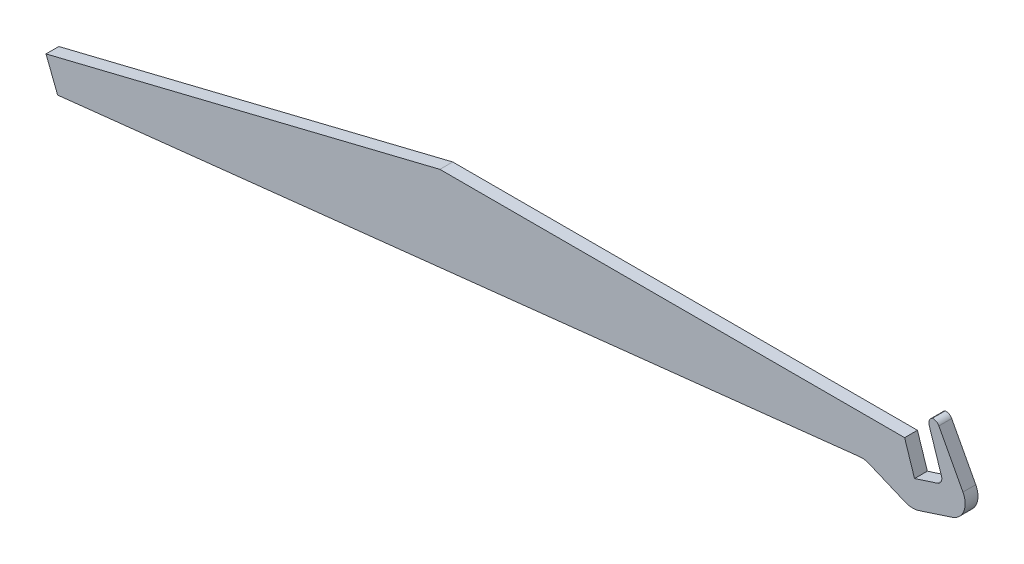
SolidWorks part; units mm, degrees
ref_plane "Front Plane" through (0, 0, 0) normal (0, 0, 1) x (1, 0, 0)
ref_plane "Top Plane" through (0, 0, 0) normal (0, 1, 0) x (1, 0, 0)
ref_plane "Right Plane" through (0, 0, 0) normal (1, 0, 0) x (0, 0, -1)
sketch "Sketch1" plane through (0, 0, 0) normal (0, 0, 1) x (1, 0, 0)
  line L0 (0, 0) -> (145, 0)
  line L1 (145, 0) -> (148.0902, -9.5106)
  line L2 (148.0902, -9.5106) -> (157.1252, -6.5749)
  line L3 (157.1252, -6.5749) -> (152.0409, 9.0729)
  line L5 (152.0409, 9.0729) -> (154.8941, 10)
  line L6 (154.8941, 10) -> (166.5512, -11.9239)
  line L7 (166.5512, -11.9239) -> (147.2522, -18.1945)
  line L8 (147.2522, -18.1945) -> (132.5, -12)
  line L9 (132.5, -12) -> (0, -26.5111)
  line L10 (0, -26.5111) -> (0, 0) construction
  line L11 (0, -26.5111) -> (-119.2868, -39.5751)
  line L12 (-119.2868, -39.5751) -> (-122.9111, -30.2551)
  line L13 (-122.9111, -30.2551) -> (0, 0)
  point P7 (0, 0)
  dimension "D2" = 3
  dimension "D3" = 105
  dimension "D4" = 10
  dimension "D5" = 9.5
  dimension "D6" = 10
  dimension "D7" = 120
  dimension "D8" = 8
  dimension "D9" = 6.25
  dimension "D10" = 16
  dimension "D11" = 145
  dimension "D12" = 10
  dimension "D13" = 10
  dimension "D14" = 108
  dimension "D15" = 12
  dimension "D16" = 132.5
extrude "Boss-Extrude1" add sketch "Sketch1" along normal blind 4
fillet "Fillet1" radius 2 3 edges at (157.1252, -6.5749, 2) (152.0409, 9.0729, 2) (154.8941, 10, 2)
fillet "Fillet2" radius 6 3 edges at (132.5, -12, 2) (147.2522, -18.1945, 2) (166.5512, -11.9239, 2)
